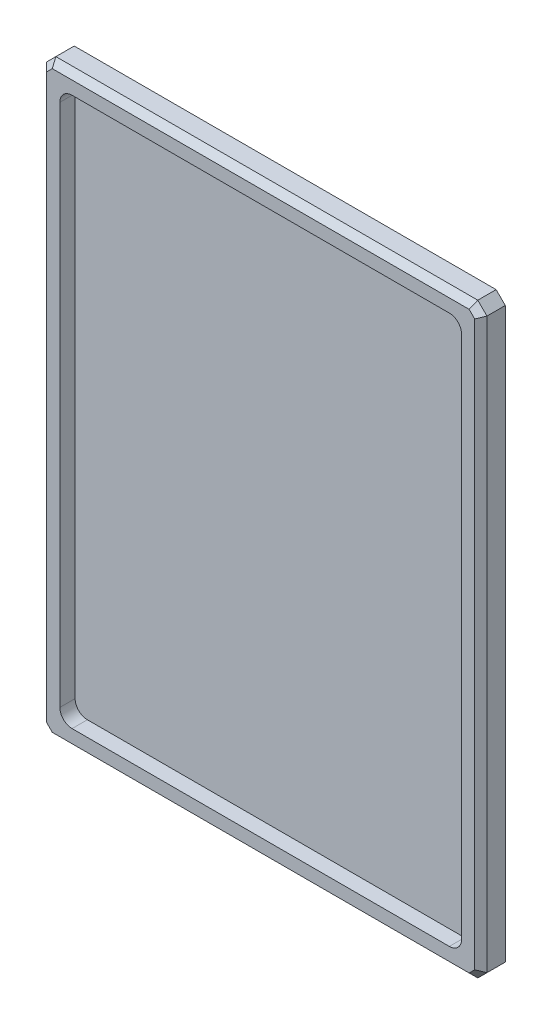
SolidWorks part; units mm, degrees
material "AISI 304"
ref_plane "Front Plane" through (0, 0, 0) normal (0, 0, 1) x (1, 0, 0)
ref_plane "Top Plane" through (0, 0, 0) normal (0, 1, 0) x (1, 0, 0)
ref_plane "Right Plane" through (0, 0, 0) normal (1, 0, 0) x (0, 0, -1)
sketch "Sketch1" plane through (0, 0, 0) normal (0, 0, 1) x (1, 0, 0)
  line L1 (114.3, -152.4) -> (-114.3, -152.4)
  line L2 (114.3, -152.4) -> (114.3, 152.4)
  line L3 (114.3, 152.4) -> (-114.3, 152.4)
  line L4 (-114.3, -152.4) -> (-114.3, 152.4)
  line L5 (114.3, -152.4) -> (-114.3, 152.4) construction
  line L6 (114.3, 152.4) -> (-114.3, -152.4) construction
  point P0 (0, 0)
  dimension "D1" = 228.6
  dimension "D2" = 304.8
extrude "Boss-Extrude1" add sketch "Sketch1" along normal blind 12.7
sketch "Sketch2" plane through (0, 0, 12.7) normal (0, 0, 1) x (1, 0, 0)
  line L0 (-114.3, 152.4) -> (-114.3, -152.4) construction
  line L1 (97.95, -142.4) -> (-97.95, -142.4)
  line L2 (104.3, -136.05) -> (104.3, 136.05)
  line L3 (97.95, 142.4) -> (-97.95, 142.4)
  line L4 (-104.3, -136.05) -> (-104.3, 136.05)
  line L5 (104.3, -142.4) -> (-104.3, 142.4) construction
  line L6 (104.3, 142.4) -> (-104.3, -142.4) construction
  line L7 (114.3, 152.4) -> (-114.3, 152.4) construction
  arc A0 (-97.95, -142.4) -> (-104.3, -136.05) centre (-97.95, -136.05) cw
  arc A1 (97.95, -142.4) -> (104.3, -136.05) centre (97.95, -136.05) ccw
  arc A2 (104.3, 136.05) -> (97.95, 142.4) centre (97.95, 136.05) ccw
  arc A3 (-97.95, 142.4) -> (-104.3, 136.05) centre (-97.95, 136.05) ccw
  point P0 (0, 0)
  dimension "D3" = 6.35
  dimension "D1" = 10
  dimension "D2" = 10
extrude "Cut-Extrude1" cut sketch "Sketch2" against normal blind 7.9375
chamfer "Chamfer1" distance 4.7625 angle 45 4 edges at (-114.3, -152.4, 6.35) (114.3, -152.4, 6.35) (-114.3, 152.4, 6.35) (114.3, 152.4, 6.35)
chamfer "Chamfer2" distance 3.175 angle 45 8 edges at (-111.9188, 150.0187, 12.7) (0, 152.4, 12.7) (-114.3, 0, 12.7) (-111.9188, -150.0188, 12.7) (0, -152.4, 12.7) (111.9187, -150.0188, 12.7) (114.3, 0, 12.7) (111.9187, 150.0187, 12.7)
